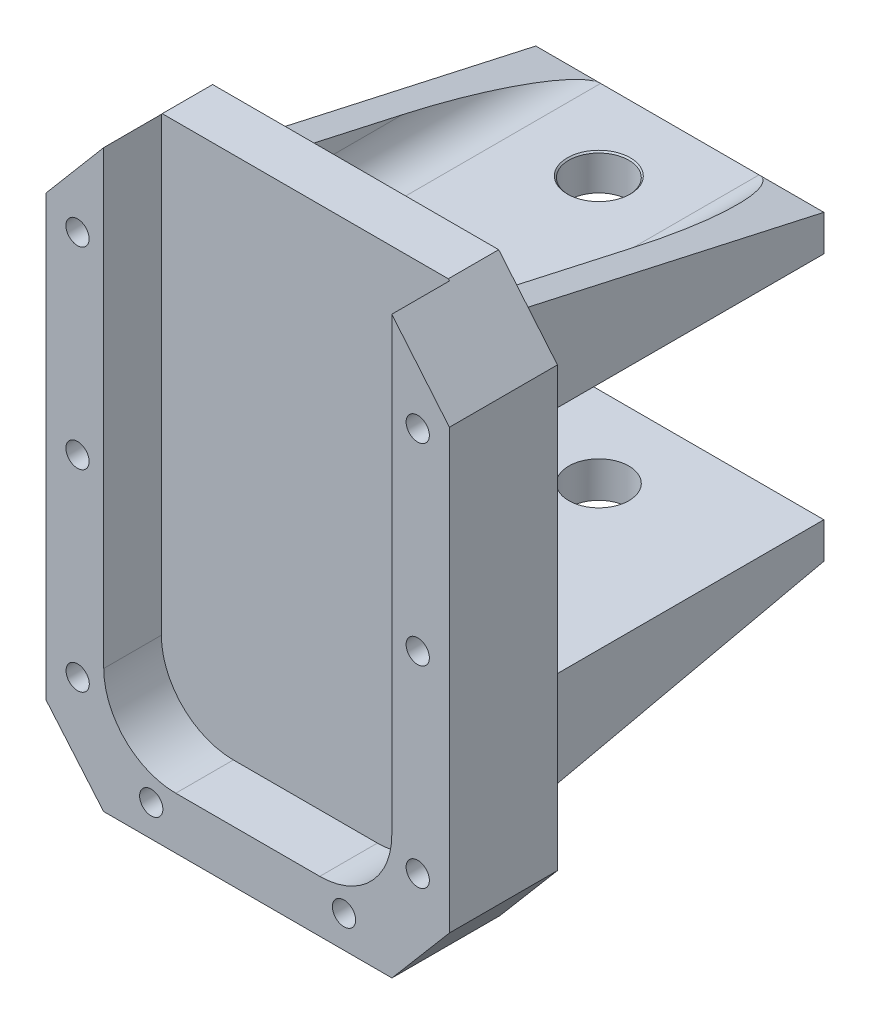
SolidWorks part; units mm, degrees
material "PLA"
ref_plane "Front Plane" through (0, 0, 0) normal (0, 0, 1) x (1, 0, 0)
ref_plane "Top Plane" through (0, 0, 0) normal (0, 1, 0) x (1, 0, 0)
ref_plane "Right Plane" through (0, 0, 0) normal (1, 0, 0) x (0, 0, -1)
sketch "Sketch1" plane through (0, 0, 0) normal (0, 0, 1) x (1, 0, 0)
  line L1 (0, 0) -> (-35.56, 0)
  line L2 (0, 0) -> (0, 50.8)
  line L3 (0, 50.8) -> (-35.56, 50.8)
  line L4 (-35.56, 0) -> (-35.56, 50.8)
  dimension "D1" = 50.8
  dimension "D2" = 35.56
extrude "Boss-Extrude1" add sketch "Sketch1" along normal blind 9.525
sketch "Sketch2" plane through (0, 0, 9.525) normal (0, 0, 1) x (1, 0, 0)
  line L0 (0, 50.8) -> (-35.56, 50.8) construction
  line L1 (-30.48, 50.8) -> (-5.08, 50.8)
  line L2 (-30.48, 50.8) -> (-30.48, 4.58)
  line L3 (-30.48, 4.58) -> (-5.08, 4.58)
  line L4 (-5.08, 50.8) -> (-5.08, 4.58)
  line L5 (-35.56, 0) -> (0, 0) construction
  line L6 (-17.78, 0) -> (-17.78, 4.58) construction
  dimension "D1" = 46.22
  dimension "D2" = 25.4
extrude "Cut-Extrude2" cut sketch "Sketch2" against normal blind 5.08
hole_wizard "Tap Drill for M2.5x0.45 Tap1" positions "Sketch6" profile "Sketch5" hole size "M2.5x0.45" standard "ANSI Metric" end condition through all
sketch "Sketch6" plane through (0, 0, 0) normal (0, 0, -1) x (-1, 0, 0)
  point P0 (2.7924, 43.0871)
  point P2 (2.7924, 26.093)
  point P4 (2.7924, 9.1052)
  point P6 (9.2907, 2.8227)
  point P8 (26.2924, 2.7871)
  point P10 (32.78, 9.1052)
  point P12 (32.7924, 26.0871)
  point P14 (32.7924, 43.0871)
sketch "Sketch5" plane through (-2.7924, 43.0871, 0) normal (1, 0, 0) x (0, 1, 0)
  line L0 (0, 0) -> (0, 9.525)
  line L1 (0, 9.525) -> (1.025, 9.525)
  line L2 (1.025, 9.525) -> (1.025, 0)
  line L5 (1.025, 0) -> (0, 0)
  line L11 (0, -6.35) -> (0, 107.95) construction
  dimension "Thru Hole Dia." = 2.05
  dimension "Thru Hole Depth" = 9.525
sketch "Sketch13" plane through (0, 0, 0) normal (0, 0, -1) x (-1, 0, 0)
  line L0 (35.56, 0) -> (0, 0) construction
  line L1 (30.48, 39.415) -> (5.08, 39.415)
  line L2 (30.48, 39.415) -> (30.48, 36.24)
  line L3 (30.48, 36.24) -> (5.08, 36.24)
  line L4 (5.08, 39.415) -> (5.08, 36.24)
  line L5 (30.48, 39.415) -> (5.08, 36.24) construction
  line L6 (30.48, 36.24) -> (5.08, 39.415) construction
  line L7 (30.48, 15.94) -> (5.08, 15.94)
  line L8 (30.48, 15.94) -> (30.48, 12.765)
  line L9 (30.48, 12.765) -> (5.08, 12.765)
  line L10 (5.08, 15.94) -> (5.08, 12.765)
  line L11 (30.48, 15.94) -> (5.08, 12.765) construction
  line L12 (30.48, 12.765) -> (5.08, 15.94) construction
  line L13 (17.78, 15.94) -> (17.78, 36.24) construction
  line L15 (0, 50.8) -> (35.56, 50.8) construction
  point P0 (17.78, 37.8275)
  point P5 (17.78, 14.3525)
  point P12 (17.78, 0)
  point P15 (17.78, 26.09)
  dimension "D1" = 3.175
  dimension "D2" = 3.175
  dimension "D3" = 25.4
  dimension "D4" = 20.3
  dimension "D5" = 24.71
extrude "Boss-Extrude2" add sketch "Sketch13" along normal blind 28.575
sketch "Sketch8" plane through (0, 0, 9.525) normal (0, 0, 1) x (1, 0, 0)
  line L0 (-5.179, 50.8) -> (0, 44.5915)
  line L1 (-5.08, 50.8) -> (-30.48, 50.8) construction
  line L2 (0, 0) -> (0, 50.8) construction
  line L3 (0.0027, 44.5883) -> (-5.0973, 50.5883) construction
  line L4 (0, 44.5915) -> (0, 50.8)
  line L5 (0, 50.8) -> (-5.179, 50.8)
  line L6 (-35.56, 44.7066) -> (-35.56, 50.8)
  line L7 (-35.56, 50.8) -> (-35.56, 0) construction
  line L8 (-35.56, 50.8) -> (-30.4026, 50.8)
  line L9 (-30.4026, 50.8) -> (-35.56, 44.7066)
  line L10 (-35.56, 5.97) -> (-35.56, 0)
  line L11 (-35.56, 0) -> (-30.4926, 0)
  line L12 (-35.56, 0) -> (0, 0) construction
  line L13 (-30.4926, 0) -> (-35.56, 5.97)
  line L14 (-5.0926, -0.0313) -> (0, 0)
  line L15 (0, 0) -> (0, 5.97)
  line L16 (0, 5.97) -> (-5.0926, -0.0313)
extrude "Cut-Extrude3" cut sketch "Sketch8" against normal through all
ref_plane "Plane6" through (-23.56, 0, 0) normal (-1, 0, 0) x (0, 0, 1)
fillet "Fillet1" radius 6.35 2 edges at (-5.08, 4.58, 6.985) (-30.48, 4.58, 6.985)
sketch "Sketch10" plane through (-43.87, 39.415, 0) normal (0, -1, 0) x (0, 0, -1)
  line L2 (14.2875, 13.39) -> (14.2875, 38.79) construction
  line L3 (0, 38.79) -> (0, 13.39) construction
  line L4 (14.2875, 26.09) -> (0, 26.09) construction
  line L6 (28.575, 13.39) -> (0, 13.39) construction
  line L7 (28.575, 38.79) -> (0, 38.79) construction
  line L8 (14.2875, 26.09) -> (28.575, 26.09) construction
  line L9 (28.575, 38.79) -> (28.575, 13.39) construction
  circle A0 centre (21.4312, 26.09) radius 3.175
  circle A1 centre (7.1438, 26.09) radius 3.175
  dimension "D1" = 6.35
hole_wizard "M5 Clearance Hole1" positions "3DSketch1" profile "Sketch11" hole size "M5" standard "ANSI Metric" end condition through all
sketch3d "3DSketch1"
  point P0 (-17.78, 39.415, -7.1438)
  point P3 (-17.78, 39.415, -21.4312)
sketch "Sketch11" plane through (-17.78, 39.415, -7.1438) normal (1, 0, 0) x (0, 0, 1)
  line L0 (0, 0) -> (0, 39.415)
  line L1 (0, 39.415) -> (2.65, 39.415)
  line L2 (2.65, 39.415) -> (2.65, 0.125)
  line L3 (2.65, 0.125) -> (2.775, 0)
  line L5 (2.775, 0) -> (0, 0)
  line L6 (-2.65, 0.125) -> (-2.775, 0) construction
  line L11 (0, -6.35) -> (0, 107.95) construction
  dimension "Thru Hole Dia." = 5.3
  dimension "Thru Hole Depth" = 39.415
  dimension "Near C'Sink Dia." = 5.55
  dimension "Near C'Sink Angle" = 90
sketch "Sketch14" plane through (-30.48, 0, 0) normal (-1, 0, 0) x (0, 0, 1)
  line L0 (-28.575, 12.765) -> (0, 6.415)
  line L1 (0, 44.7066) -> (0, 5.97) construction
  line L2 (-28.575, 12.765) -> (0, 12.765) construction
  dimension "D1" = 6.35
rib "Rib7" sketch "Sketch14" sketch "Sketch14" thickness 2.54 extrusion direction parallel to sketch draft on no parameters "D1"=2.54
sketch "Sketch15" plane through (-5.08, 0, 0) normal (1, 0, 0) x (0, 0, -1)
  line L0 (28.575, 12.765) -> (0, 6.415)
rib "Rib8" sketch "Sketch15" sketch "Sketch15" thickness 2.54 extrusion direction parallel to sketch draft on no parameters "D1"=2.54
sketch "Sketch16" plane through (-30.48, 0, 0) normal (-1, 0, 0) x (0, 0, 1)
  line L0 (-28.575, 39.415) -> (0, 45.765)
  line L1 (0, 44.7066) -> (0, 5.97) construction
  dimension "D1" = 6.35
sketch "Sketch17" plane through (-5.08, 0, 0) normal (1, 0, 0) x (0, 0, -1)
  line L0 (28.575, 39.415) -> (0, 45.765)
rib "Rib9" sketch "Sketch17" sketch "Sketch17" thickness 2.54 extrusion direction parallel to sketch draft on no parameters "D1"=2.54
rib "Rib10" sketch "Sketch16" sketch "Sketch16" thickness 2.54 extrusion direction parallel to sketch draft on no parameters "D1"=2.54
fillet "Fillet2" radius 3.175 2 edges at (-27.94, 12.765, -14.2875) (-7.62, 12.765, -14.2875)
fillet "Fillet3" radius 3.175 2 edges at (-7.62, 39.415, -14.2875) (-27.94, 39.415, -14.2875)
sketch "Sketch18" plane through (0, 39.415, 0) normal (0, 1, 0) x (1, 0, 0)
  line L0 (-17.78, 7.1438) -> (-17.78, 21.4312) construction
